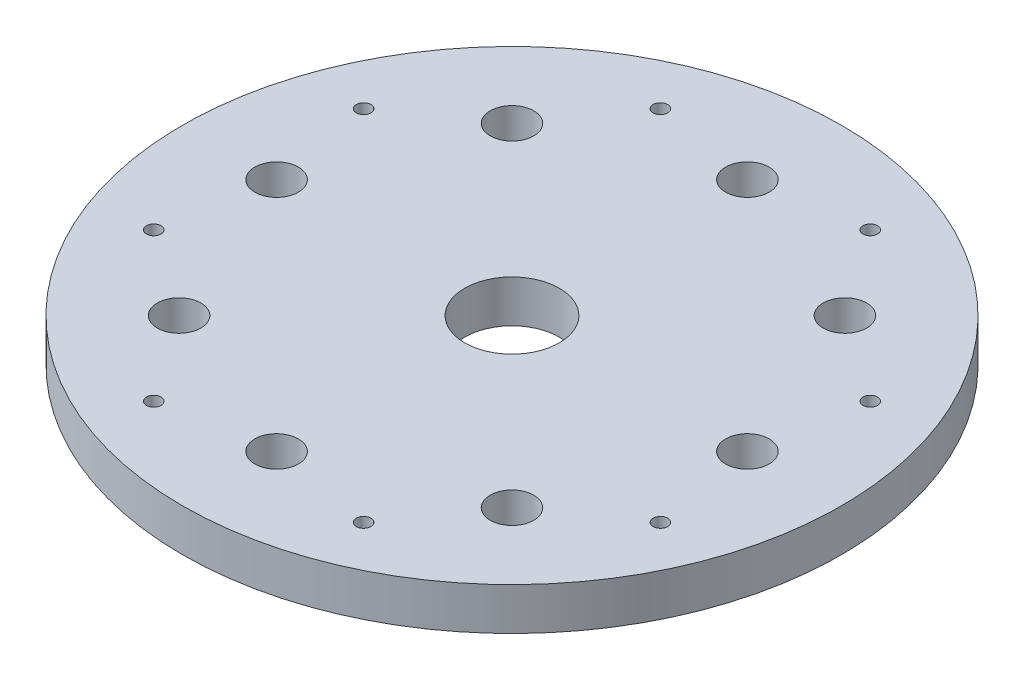
SolidWorks part; units mm, degrees
ref_plane "Front Plane" through (0, 0, 0) normal (0, 0, 1) x (1, 0, 0)
ref_plane "Top Plane" through (0, 0, 0) normal (0, 1, 0) x (1, 0, 0)
ref_plane "Right Plane" through (0, 0, 0) normal (1, 0, 0) x (0, 0, -1)
sketch "Sketch1" plane through (0, 0, 0) normal (0, 1, 0) x (1, 0, 0)
  line L0 (70, 0) -> (50, 0) construction
  circle A0 centre (0, 0) radius 70
  circle A1 centre (50, 0) radius 12
  circle A2 centre (35.3553, -35.3553) radius 12
  circle A3 centre (0, -50) radius 12
  circle A4 centre (-35.3553, -35.3553) radius 12
  circle A5 centre (-50, 0) radius 12
  circle A6 centre (-35.3553, 35.3553) radius 12
  circle A7 centre (0, 50) radius 12
  circle A8 centre (35.3553, 35.3553) radius 12
  point P23 (0, 0)
  dimension "D1" = 140
  dimension "D3" = 24
  dimension "D2" = 20
  dimension "D4" = 8
extrude "Boss-Extrude1" add sketch "Sketch1" along normal blind 25
sketch "Sketch2" plane through (0, 25, 0) normal (0, 1, 0) x (1, 0, 0)
  line L0 (50, 0) -> (50, 16) construction
  line L1 (50, 16) -> (43.4205, 16)
  line L2 (50, 16) -> (56.5795, 16)
  line L3 (32.7, 0) -> (67.3, 0) construction
  line L4 (50, -16) -> (56.5795, -16)
  line L5 (50, -16) -> (43.4205, -16)
  line L6 (46.669, -24.0416) -> (42.0166, -19.3892)
  line L7 (24.0416, -46.669) -> (19.3892, -42.0166)
  line L8 (24.0416, -46.669) -> (28.694, -51.3215)
  line L9 (46.669, -24.0416) -> (51.3215, -28.694)
  line L10 (16, -50) -> (16, -43.4205)
  line L11 (-16, -50) -> (-16, -43.4205)
  line L12 (-16, -50) -> (-16, -56.5795)
  line L13 (16, -50) -> (16, -56.5795)
  line L14 (-24.0416, -46.669) -> (-19.3892, -42.0166)
  line L15 (-46.669, -24.0416) -> (-42.0166, -19.3892)
  line L16 (-46.669, -24.0416) -> (-51.3215, -28.694)
  line L17 (-24.0416, -46.669) -> (-28.694, -51.3215)
  line L18 (-50, -16) -> (-43.4205, -16)
  line L19 (-50, 16) -> (-43.4205, 16)
  line L20 (-50, 16) -> (-56.5795, 16)
  line L21 (-50, -16) -> (-56.5795, -16)
  line L22 (-46.669, 24.0416) -> (-42.0166, 19.3892)
  line L23 (-24.0416, 46.669) -> (-19.3892, 42.0166)
  line L24 (-24.0416, 46.669) -> (-28.694, 51.3215)
  line L25 (-46.669, 24.0416) -> (-51.3215, 28.694)
  line L26 (-16, 50) -> (-16, 43.4205)
  line L27 (16, 50) -> (16, 43.4205)
  line L28 (16, 50) -> (16, 56.5795)
  line L29 (-16, 50) -> (-16, 56.5795)
  line L30 (24.0416, 46.669) -> (19.3892, 42.0166)
  line L31 (46.669, 24.0416) -> (42.0166, 19.3892)
  line L32 (46.669, 24.0416) -> (51.3215, 28.694)
  line L33 (24.0416, 46.669) -> (28.694, 51.3215)
  arc A0 (43.4205, 16) -> (43.4205, -16) centre (50, 0) ccw
  arc A1 (56.5795, -16) -> (56.5795, 16) centre (50, 0) ccw
  arc A2 (42.0166, -19.3892) -> (19.3892, -42.0166) centre (35.3553, -35.3553) ccw
  arc A3 (28.694, -51.3215) -> (51.3215, -28.694) centre (35.3553, -35.3553) ccw
  arc A4 (16, -43.4205) -> (-16, -43.4205) centre (0, -50) ccw
  arc A5 (-16, -56.5795) -> (16, -56.5795) centre (0, -50) ccw
  arc A6 (-19.3892, -42.0166) -> (-42.0166, -19.3892) centre (-35.3553, -35.3553) ccw
  arc A7 (-51.3215, -28.694) -> (-28.694, -51.3215) centre (-35.3553, -35.3553) ccw
  arc A8 (-43.4205, -16) -> (-43.4205, 16) centre (-50, 0) ccw
  arc A9 (-56.5795, 16) -> (-56.5795, -16) centre (-50, 0) ccw
  arc A10 (-42.0166, 19.3892) -> (-19.3892, 42.0166) centre (-35.3553, 35.3553) ccw
  arc A11 (-28.694, 51.3215) -> (-51.3215, 28.694) centre (-35.3553, 35.3553) ccw
  arc A12 (-16, 43.4205) -> (16, 43.4205) centre (0, 50) ccw
  arc A13 (16, 56.5795) -> (-16, 56.5795) centre (0, 50) ccw
  arc A14 (19.3892, 42.0166) -> (42.0166, 19.3892) centre (35.3553, 35.3553) ccw
  arc A15 (51.3215, 28.694) -> (28.694, 51.3215) centre (35.3553, 35.3553) ccw
  point P61 (0, 0)
  dimension "D1" = 34.6
  dimension "D2" = 16
  dimension "D3" = 8
extrude "Cut-Extrude1" cut sketch "Sketch2" against normal blind 10
ref_plane "Plane1" through (0, 10, 0) normal (0, 1, 0) x (1, 0, 0)
split "Split1" trim tools "Plane1" bodies to split 102 resulting bodies 103 104
delete or keep bodies "Body-Delete/Keep 1" type delete bodies bodies 104
sketch "Sketch3" plane through (0, 10, 0) normal (0, -1, 0) x (1, 0, 0)
  circle A0 centre (0, 0) radius 20
  dimension "D1" = 40
extrude "Cut-Extrude2" cut sketch "Sketch3" against normal blind 7.5
sketch "Sketch4" plane through (0, 25, 0) normal (0, 1, 0) x (1, 0, 0)
  circle A0 centre (0, 0) radius 70
extrude "Cut-Extrude3" cut sketch "Sketch4" against normal blind 6
sketch "Sketch5" plane through (0, 19, 0) normal (0, 1, 0) x (1, 0, 0)
  line L0 (-70, 0) -> (70, 0) construction
  line L1 (0, 4) -> (0, -4) construction
  circle A1 centre (0, 0) radius 70 construction
  circle A2 centre (0, -4) radius 1.5
  circle A3 centre (0, 4) radius 1.5
  circle A4 centre (-4, 0) radius 1.5
  circle A5 centre (4, 0) radius 1.5
  point P11 (0, 0)
  dimension "D1" = 3
  dimension "D3" = 4
  dimension "D2" = 8
extrude "Cut-Extrude4" cut sketch "Sketch5" against normal through all
sketch "Sketch6" plane through (0, 19, 0) normal (0, 1, 0) x (1, 0, 0)
  line L0 (-16, 43.4205) -> (-19.3892, 42.0166) construction
  line L1 (-17.6946, 42.7186) -> (-26.7878, 64.6716) construction
  circle A0 centre (0, 0) radius 70 construction
  circle A1 centre (-22.2868, 53.8051) radius 1.55
  circle A2 centre (22.2868, 53.8051) radius 1.55
  circle A3 centre (53.8051, 22.2868) radius 1.55
  circle A4 centre (53.8051, -22.2868) radius 1.55
  circle A5 centre (22.2868, -53.8051) radius 1.55
  circle A6 centre (-22.2868, -53.8051) radius 1.55
  circle A7 centre (-53.8051, -22.2868) radius 1.55
  circle A8 centre (-53.8051, 22.2868) radius 1.55
  point P19 (0, 0)
  dimension "D1" = 12
  dimension "D3" = 3.1
  dimension "D2" = 21.953
  dimension "D4" = 8
sketch "Sketch7" plane through (0, 17.5, 0) normal (0, -1, 0) x (1, 0, 0)
  circle A0 centre (0, 0) radius 20
extrude "Boss-Extrude2" add sketch "Sketch7" along normal up to surface and the other way up to surface up to face at (0, 10, -20) other way up to face at (0, 19, 5.5)
sketch "Sketch9" plane through (0, 10, 0) normal (0, -1, 0) x (1, 0, 0)
  circle A0 centre (0, 50) radius 12
  circle A1 centre (0, 50) radius 2.4904
  circle A2 centre (35.3553, 35.3553) radius 2.4904
  circle A3 centre (35.3553, 35.3553) radius 12
  circle A4 centre (50, 0) radius 2.4904
  circle A5 centre (50, 0) radius 12
  circle A6 centre (35.3553, -35.3553) radius 2.4904
  circle A7 centre (35.3553, -35.3553) radius 12
  circle A8 centre (0, -50) radius 2.4904
  circle A9 centre (0, -50) radius 12
  circle A10 centre (-35.3553, -35.3553) radius 2.4904
  circle A11 centre (-35.3553, -35.3553) radius 12
  circle A12 centre (-50, 0) radius 2.4904
  circle A13 centre (-50, 0) radius 12
  circle A14 centre (-35.3553, 35.3553) radius 2.4904
  circle A15 centre (-35.3553, 35.3553) radius 12
  point P28 (0, 0)
  dimension "D1" = 8
extrude "Boss-Extrude3" add sketch "Sketch9" against normal up to surface (9 mm away) up to face at (35.3553, 19, 35.3553)
extrude "Cut-Extrude5" cut sketch "Sketch6" against normal through all
sketch "Sketch10" plane through (0, 15, 0) normal (0, 1, 0) x (1, 0, 0)
  line L0 (16, -56.5795) -> (16, -43.4205)
  line L1 (-16, -56.5795) -> (-16, -43.4205)
  line L16 (-28.694, -51.3215) -> (-19.3892, -42.0166)
  line L17 (-51.3215, -28.694) -> (-42.0166, -19.3892)
  line L18 (-56.5795, -16) -> (-43.4205, -16)
  line L19 (-56.5795, 16) -> (-43.4205, 16)
  line L20 (-51.3215, 28.694) -> (-42.0166, 19.3892)
  line L21 (-28.694, 51.3215) -> (-19.3892, 42.0166)
  line L22 (-16, 56.5795) -> (-16, 43.4205)
  line L23 (16, 56.5795) -> (16, 43.4205)
  line L24 (28.694, 51.3215) -> (19.3892, 42.0166)
  line L25 (51.3215, 28.694) -> (42.0166, 19.3892)
  line L26 (56.5795, 16) -> (43.4205, 16)
  line L27 (56.5795, -16) -> (43.4205, -16)
  line L28 (51.3215, -28.694) -> (42.0166, -19.3892)
  line L29 (28.694, -51.3215) -> (19.3892, -42.0166)
  arc A0 (16, -43.4205) -> (-16, -43.4205) centre (0, -50) ccw
  arc A1 (-16, -56.5795) -> (16, -56.5795) centre (0, -50) ccw
  circle A16 centre (0, -50) radius 2.4904
  arc A17 (-19.3892, -42.0166) -> (-42.0166, -19.3892) centre (-35.3553, -35.3553) ccw
  arc A18 (-51.3215, -28.694) -> (-28.694, -51.3215) centre (-35.3553, -35.3553) ccw
  circle A19 centre (-35.3553, -35.3553) radius 2.4904
  arc A20 (-43.4205, -16) -> (-43.4205, 16) centre (-50, 0) ccw
  arc A21 (-56.5795, 16) -> (-56.5795, -16) centre (-50, 0) ccw
  circle A22 centre (-50, 0) radius 2.4904
  arc A23 (-42.0166, 19.3892) -> (-19.3892, 42.0166) centre (-35.3553, 35.3553) ccw
  arc A24 (-28.694, 51.3215) -> (-51.3215, 28.694) centre (-35.3553, 35.3553) ccw
  circle A25 centre (-35.3553, 35.3553) radius 2.4904
  arc A26 (-16, 43.4205) -> (16, 43.4205) centre (0, 50) ccw
  arc A27 (16, 56.5795) -> (-16, 56.5795) centre (0, 50) ccw
  circle A28 centre (0, 50) radius 2.4904
  arc A29 (19.3892, 42.0166) -> (42.0166, 19.3892) centre (35.3553, 35.3553) ccw
  arc A30 (51.3215, 28.694) -> (28.694, 51.3215) centre (35.3553, 35.3553) ccw
  circle A31 centre (35.3553, 35.3553) radius 2.4904
  arc A32 (43.4205, 16) -> (43.4205, -16) centre (50, 0) ccw
  arc A33 (56.5795, -16) -> (56.5795, 16) centre (50, 0) ccw
  circle A34 centre (50, 0) radius 2.4904
  arc A35 (42.0166, -19.3892) -> (19.3892, -42.0166) centre (35.3553, -35.3553) ccw
  arc A36 (28.694, -51.3215) -> (51.3215, -28.694) centre (35.3553, -35.3553) ccw
  circle A37 centre (35.3553, -35.3553) radius 2.4904
  point P49 (0, 0)
  point P58 (0, 0)
  dimension "D1" = 8
extrude "Boss-Extrude5" add sketch "Sketch10" along normal up to surface (4 mm away) up to face at (-53.8051, 19, -20.7368)
sketch "Sketch11" plane through (0, 19, 0) normal (0, 1, 0) x (1, 0, 0)
  circle A0 centre (0, 0) radius 10.0532
extrude "Cut-Extrude7" cut sketch "Sketch11" against normal through all
sketch "Sketch12" plane through (0, 10, 0) normal (0, -1, 0) x (1, 0, 0)
  circle A1 centre (-35.3553, 35.3553) radius 2.4904
  circle A2 centre (-35.3553, 35.3553) radius 1.75
  circle A3 centre (0, 50) radius 2.4904
  circle A4 centre (0, 50) radius 1.75
  circle A5 centre (35.3553, 35.3553) radius 2.4904
  circle A6 centre (35.3553, 35.3553) radius 1.75
  circle A7 centre (50, 0) radius 2.4904
  circle A8 centre (50, 0) radius 1.75
  circle A9 centre (35.3553, -35.3553) radius 2.4904
  circle A10 centre (35.3553, -35.3553) radius 1.75
  circle A11 centre (0, -50) radius 2.4904
  circle A12 centre (0, -50) radius 1.75
  circle A13 centre (-35.3553, -35.3553) radius 2.4904
  circle A14 centre (-35.3553, -35.3553) radius 1.75
  circle A15 centre (-50, 0) radius 2.4904
  circle A16 centre (-50, 0) radius 1.75
  point P28 (0, 0)
  dimension "D1" = 3.5
  dimension "D2" = 8
extrude "Boss-Extrude6" add sketch "Sketch12" against normal up to surface (9 mm away) up to face at (0, 19, 10.0532)
sketch "Sketch13" plane through (0, 10, 0) normal (0, -1, 0) x (1, 0, 0)
  circle A0 centre (-35.3553, 35.3553) radius 1.75
  circle A1 centre (-35.3553, 35.3553) radius 4.625
  circle A2 centre (0, 50) radius 1.75
  circle A3 centre (0, 50) radius 4.625
  circle A4 centre (35.3553, 35.3553) radius 1.75
  circle A5 centre (35.3553, 35.3553) radius 4.625
  circle A6 centre (50, 0) radius 1.75
  circle A7 centre (50, 0) radius 4.625
  circle A8 centre (35.3553, -35.3553) radius 1.75
  circle A9 centre (35.3553, -35.3553) radius 4.625
  circle A10 centre (0, -50) radius 1.75
  circle A11 centre (0, -50) radius 4.625
  circle A12 centre (-35.3553, -35.3553) radius 1.75
  circle A13 centre (-35.3553, -35.3553) radius 4.625
  circle A14 centre (-50, 0) radius 1.75
  circle A15 centre (-50, 0) radius 4.625
  point P28 (0, 0)
  dimension "D1" = 9.25
  dimension "D2" = 8
extrude "Cut-Extrude8" cut sketch "Sketch13" against normal through all
